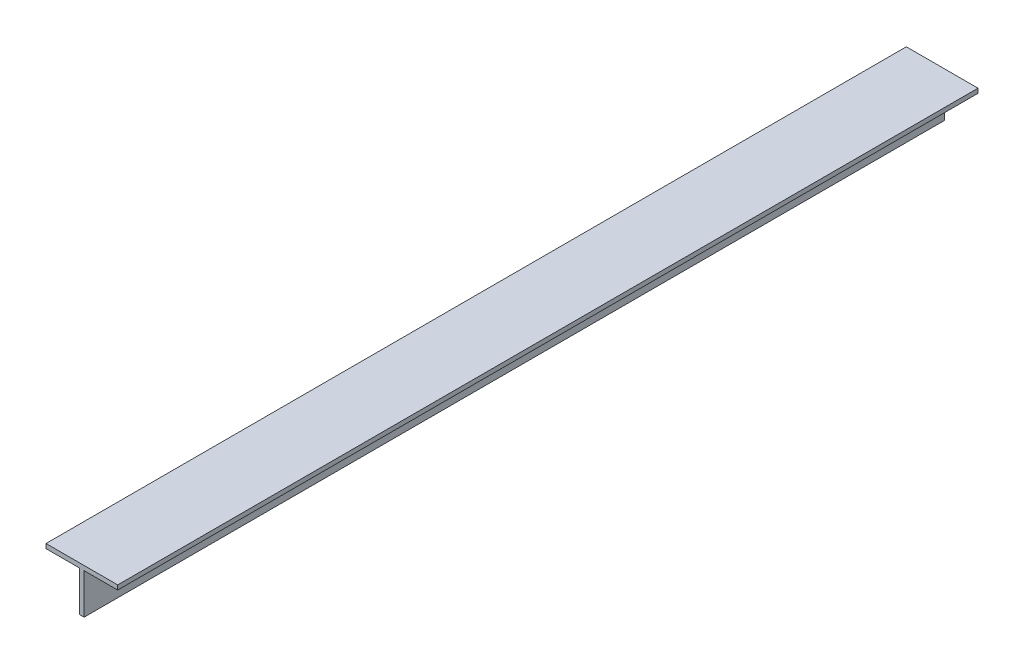
SolidWorks part; units mm, degrees
ref_plane "Front" through (0, 0, 0) normal (0, 0, 1) x (1, 0, 0)
ref_plane "Top" through (0, 0, 0) normal (0, 1, 0) x (1, 0, 0)
ref_plane "Right" through (0, 0, 0) normal (1, 0, 0) x (0, 0, -1)
sketch "Sketch1" plane through (0, 0, 0) normal (0, 0, 1) x (1, 0, 0)
  line L0 (-25.4, 31.75) -> (-25.4, 28.575)
  line L1 (-25.4, 28.575) -> (-1.5875, 28.575)
  line L2 (-1.5875, 28.575) -> (-1.5875, 0)
  line L3 (-1.5875, 0) -> (1.5875, 0)
  line L4 (1.5875, 0) -> (1.5875, 28.575)
  line L5 (1.5875, 28.575) -> (25.4, 28.575)
  line L6 (25.4, 28.575) -> (25.4, 31.75)
  line L7 (25.4, 31.75) -> (-25.4, 31.75)
  dimension "Thickness" = 3.175
  dimension "Width" = 50.8
  dimension "Height" = 31.75
extrude "Boss-Extrude1" add sketch "Sketch1" along normal mid plane 609.6
sketch "Sketch2" plane through (1.5875, 0, 0) normal (1, 0, 0) x (0, 0, -1)
  line L0 (0, 15.875) -> (0, 147.1907) construction
  line L1 (-304.8, 28.575) -> (304.8, 28.575) construction
  circle A0 centre (-228.6, 15.875) radius 3.5
  circle A1 centre (228.6, 15.875) radius 3.5
  dimension "D1" = 7
  dimension "D3" = 12.7
  dimension "D2" = 12.7
  dimension "D4" = 228.6
extrude "Cut-Extrude1" cut sketch "Sketch2" against normal through all
